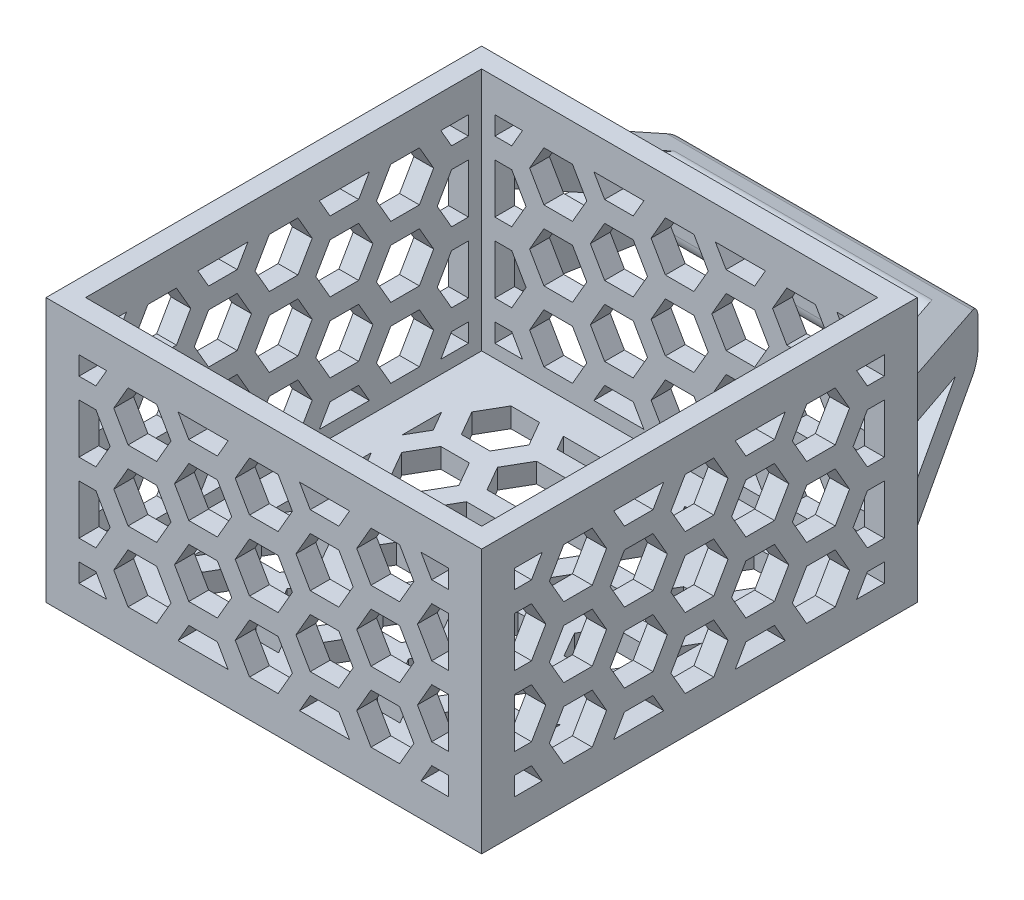
SolidWorks part; units mm, degrees
ref_plane "Front Plane" through (0, 0, 0) normal (0, 0, 1) x (1, 0, 0)
ref_plane "Top Plane" through (0, 0, 0) normal (0, 1, 0) x (1, 0, 0)
ref_plane "Right Plane" through (0, 0, 0) normal (1, 0, 0) x (0, 0, -1)
sketch "Sketch1" plane through (0, 0, 0) normal (0, 1, 0) x (1, 0, 0)
  line L0 (50, -50) -> (50, 50) construction
  line L1 (60, -60) -> (-60, -60)
  line L2 (60, -60) -> (60, 60)
  line L3 (60, 60) -> (-60, 60)
  line L4 (-60, -60) -> (-60, 60)
  line L5 (60, -60) -> (-60, 60) construction
  line L6 (60, 60) -> (-60, -60) construction
  line L7 (50, 50) -> (-50, 50) construction
  line L8 (-50, -50) -> (-50, 50) construction
  line L9 (50, -50) -> (-50, -50) construction
  line L10 (8.6603, 21.25) -> (4.3301, 28.75)
  line L11 (8.6603, 0) -> (4.3301, 7.5)
  line L12 (4.3301, 7.5) -> (-4.3301, 7.5)
  line L13 (-4.3301, 7.5) -> (-8.6603, 0)
  line L14 (-8.6603, 0) -> (-4.3301, -7.5)
  line L15 (-4.3301, -7.5) -> (4.3301, -7.5)
  line L16 (4.3301, -7.5) -> (8.6603, 0)
  line L17 (4.3301, 28.75) -> (-4.3301, 28.75)
  line L18 (-4.3301, 28.75) -> (-8.6603, 21.25)
  line L19 (-8.6603, 21.25) -> (-4.3301, 13.75)
  line L20 (-4.3301, 13.75) -> (4.3301, 13.75)
  line L21 (4.3301, 13.75) -> (8.6603, 21.25)
  line L22 (8.6603, 42.5) -> (4.3301, 50)
  line L23 (4.3301, 50) -> (-4.3301, 50)
  line L24 (-4.3301, 50) -> (-8.6603, 42.5)
  line L25 (-8.6603, 42.5) -> (-4.3301, 35)
  line L26 (-4.3301, 35) -> (4.3301, 35)
  line L27 (4.3301, 35) -> (8.6603, 42.5)
  line L28 (8.6603, -21.25) -> (4.3301, -13.75)
  line L29 (4.3301, -13.75) -> (-4.3301, -13.75)
  line L30 (-4.3301, -13.75) -> (-8.6603, -21.25)
  line L31 (-8.6603, -21.25) -> (-4.3301, -28.75)
  line L32 (-4.3301, -28.75) -> (4.3301, -28.75)
  line L33 (4.3301, -28.75) -> (8.6603, -21.25)
  line L34 (8.6603, -42.5) -> (4.3301, -35)
  line L35 (4.3301, -35) -> (-4.3301, -35)
  line L36 (-4.3301, -35) -> (-8.6603, -42.5)
  line L37 (-8.6603, -42.5) -> (-4.3301, -50)
  line L38 (-4.3301, -50) -> (4.3301, -50)
  line L39 (4.3301, -50) -> (8.6603, -42.5)
  line L40 (0, 13.75) -> (0, 7.5) construction
  line L41 (0, 10.625) -> (50, 10.625) construction
  line L42 (27.0633, 31.875) -> (22.7332, 39.375)
  line L43 (27.0633, 10.625) -> (22.7332, 18.125)
  line L44 (22.7332, 18.125) -> (14.0729, 18.125)
  line L45 (14.0729, 18.125) -> (9.7428, 10.625)
  line L46 (9.7428, 10.625) -> (14.0729, 3.125)
  line L47 (14.0729, 3.125) -> (22.7332, 3.125)
  line L48 (22.7332, 3.125) -> (27.0633, 10.625)
  line L49 (22.7332, 39.375) -> (14.0729, 39.375)
  line L50 (14.0729, 39.375) -> (9.7428, 31.875)
  line L51 (9.7428, 31.875) -> (14.0729, 24.375)
  line L52 (14.0729, 24.375) -> (22.7332, 24.375)
  line L53 (22.7332, 24.375) -> (27.0633, 31.875)
  line L57 (11.547, 50) -> (14.0729, 45.625)
  line L58 (14.0729, 45.625) -> (22.7332, 45.625)
  line L59 (22.7332, 45.625) -> (25.2591, 50)
  line L60 (22.7332, 60.625) -> (14.0729, 60.625) [skipped]
  line L61 (14.0729, 60.625) -> (13.7121, 60) [skipped]
  line L62 (23.094, 60) -> (22.7332, 60.625) [skipped]
  line L63 (11.547, 50) -> (25.2591, 50)
  line L64 (-60, 0) -> (60, 0) construction
  line L65 (0, 60) -> (0, -60) construction
  line L66 (11.547, -50) -> (14.0729, -45.625)
  line L67 (14.0729, -45.625) -> (22.7332, -45.625)
  line L68 (22.7332, -45.625) -> (25.2591, -50)
  line L69 (11.547, -50) -> (25.2591, -50)
  line L70 (22.7332, -24.375) -> (27.0633, -31.875)
  line L71 (14.0729, -24.375) -> (22.7332, -24.375)
  line L72 (9.7428, -31.875) -> (14.0729, -24.375)
  line L73 (14.0729, -39.375) -> (9.7428, -31.875)
  line L74 (22.7332, -39.375) -> (14.0729, -39.375)
  line L75 (27.0633, -31.875) -> (22.7332, -39.375)
  line L76 (22.7332, -3.125) -> (27.0633, -10.625)
  line L77 (14.0729, -3.125) -> (22.7332, -3.125)
  line L78 (9.7428, -10.625) -> (14.0729, -3.125)
  line L79 (14.0729, -18.125) -> (9.7428, -10.625)
  line L80 (22.7332, -18.125) -> (14.0729, -18.125)
  line L81 (27.0633, -10.625) -> (22.7332, -18.125)
  line L82 (45.4663, 42.5) -> (41.1362, 50)
  line L83 (41.1362, 50) -> (32.476, 50)
  line L84 (32.476, 50) -> (28.1458, 42.5)
  line L85 (28.1458, 42.5) -> (32.476, 35)
  line L86 (32.476, 35) -> (41.1362, 35)
  line L87 (41.1362, 35) -> (45.4663, 42.5)
  line L88 (45.4663, 21.25) -> (41.1362, 28.75)
  line L89 (41.1362, 28.75) -> (32.476, 28.75)
  line L90 (32.476, 28.75) -> (28.1458, 21.25)
  line L91 (28.1458, 21.25) -> (32.476, 13.75)
  line L92 (32.476, 13.75) -> (41.1362, 13.75)
  line L93 (41.1362, 13.75) -> (45.4663, 21.25)
  line L94 (45.4663, 0) -> (41.1362, 7.5)
  line L95 (41.1362, 7.5) -> (32.476, 7.5)
  line L96 (32.476, 7.5) -> (28.1458, 0)
  line L97 (28.1458, 0) -> (32.476, -7.5)
  line L98 (32.476, -7.5) -> (41.1362, -7.5)
  line L99 (41.1362, -7.5) -> (45.4663, 0)
  line L100 (45.4663, -21.25) -> (41.1362, -13.75)
  line L101 (41.1362, -13.75) -> (32.476, -13.75)
  line L102 (32.476, -13.75) -> (28.1458, -21.25)
  line L103 (28.1458, -21.25) -> (32.476, -28.75)
  line L104 (32.476, -28.75) -> (41.1362, -28.75)
  line L105 (41.1362, -28.75) -> (45.4663, -21.25)
  line L106 (45.4663, -42.5) -> (41.1362, -35)
  line L107 (41.1362, -35) -> (32.476, -35)
  line L108 (32.476, -35) -> (28.1458, -42.5)
  line L109 (28.1458, -42.5) -> (32.476, -50)
  line L110 (32.476, -50) -> (41.1362, -50)
  line L111 (41.1362, -50) -> (45.4663, -42.5)
  line L118 (50, 37.8525) -> (46.5489, 31.875)
  line L119 (46.5489, 31.875) -> (50, 25.8975)
  line L124 (50, 16.6025) -> (46.5489, 10.625)
  line L125 (46.5489, 10.625) -> (50, 4.6475)
  line L131 (50, -16.6025) -> (46.5489, -10.625)
  line L132 (46.5489, -10.625) -> (50, -4.6475)
  line L137 (50, -37.8525) -> (46.5489, -31.875)
  line L138 (46.5489, -31.875) -> (50, -25.8975)
  line L144 (50, 37.8525) -> (50, 25.8975)
  line L145 (50.879, 45.625) -> (59.5392, 45.625) [skipped]
  line L146 (59.5392, 45.625) -> (60, 46.423) [skipped]
  line L147 (50.879, 24.375) -> (59.5392, 24.375) [skipped]
  line L148 (59.5392, 39.375) -> (50.879, 39.375) [skipped]
  line L149 (63.8694, 31.875) -> (60, 38.577) [skipped]
  line L150 (60, 25.173) -> (63.8694, 31.875) [skipped]
  line L151 (59.5392, 18.125) -> (50.879, 18.125) [skipped]
  line L152 (50.879, 3.125) -> (59.5392, 3.125) [skipped]
  line L153 (63.8694, 10.625) -> (60, 17.327) [skipped]
  line L154 (59.5392, 3.125) -> (60, 3.923) [skipped]
  line L155 (59.5392, -18.125) -> (50.879, -18.125) [skipped]
  line L156 (50.879, -3.125) -> (59.5392, -3.125) [skipped]
  line L157 (60, -3.923) -> (63.8694, -10.625) [skipped]
  line L158 (60, -17.327) -> (59.5392, -18.125) [skipped]
  line L159 (59.5392, -39.375) -> (50.879, -39.375) [skipped]
  line L160 (50.879, -24.375) -> (59.5392, -24.375) [skipped]
  line L161 (60, -25.173) -> (63.8694, -31.875) [skipped]
  line L162 (63.8694, -31.875) -> (60, -38.577) [skipped]
  line L163 (50.879, -45.625) -> (59.5392, -45.625) [skipped]
  line L164 (59.5392, -45.625) -> (60, -46.423) [skipped]
  line L165 (48.3531, 50) -> (50, 47.1475) [skipped]
  line L166 (47.1304, 50) -> (50, 50) [skipped]
  line L167 (50, 16.6025) -> (50, 4.6475)
  line L168 (50, -4.6475) -> (50, -16.6025)
  line L169 (50, -25.8975) -> (50, -37.8525)
  line L170 (-46.5489, -31.875) -> (-50, -25.8975)
  line L171 (48.3531, -50) -> (48.9559, -48.9559) [skipped]
  line L172 (48.3531, -50) -> (50, -50) [skipped]
  line L173 (-50, -37.8525) -> (-46.5489, -31.875)
  line L174 (-50, -25.8975) -> (-50, -37.8525)
  line L175 (-46.5489, -10.625) -> (-50, -4.6475)
  line L176 (-50, -16.6025) -> (-46.5489, -10.625)
  line L177 (-50, -4.6475) -> (-50, -16.6025)
  line L178 (-50, 16.6025) -> (-46.5489, 10.625)
  line L179 (-46.5489, 10.625) -> (-50, 4.6475)
  line L180 (-50, 16.6025) -> (-50, 4.6475)
  line L181 (-50, 37.8525) -> (-46.5489, 31.875)
  line L182 (-46.5489, 31.875) -> (-50, 25.8975)
  line L183 (-50, 37.8525) -> (-50, 25.8975)
  line L184 (-41.1362, 35) -> (-45.4663, 42.5)
  line L185 (-32.476, 35) -> (-41.1362, 35)
  line L186 (-28.1458, 42.5) -> (-32.476, 35)
  line L187 (-32.476, 50) -> (-28.1458, 42.5)
  line L188 (-41.1362, 50) -> (-32.476, 50)
  line L189 (-45.4663, 42.5) -> (-41.1362, 50)
  line L190 (-41.1362, 13.75) -> (-45.4663, 21.25)
  line L191 (-32.476, 13.75) -> (-41.1362, 13.75)
  line L192 (-28.1458, 21.25) -> (-32.476, 13.75)
  line L193 (-32.476, 28.75) -> (-28.1458, 21.25)
  line L194 (-41.1362, 28.75) -> (-32.476, 28.75)
  line L195 (-45.4663, 21.25) -> (-41.1362, 28.75)
  line L196 (-41.1362, -7.5) -> (-45.4663, 0)
  line L197 (-32.476, -7.5) -> (-41.1362, -7.5)
  line L198 (-28.1458, 0) -> (-32.476, -7.5)
  line L199 (-32.476, 7.5) -> (-28.1458, 0)
  line L200 (-41.1362, 7.5) -> (-32.476, 7.5)
  line L201 (-45.4663, 0) -> (-41.1362, 7.5)
  line L202 (-41.1362, -28.75) -> (-45.4663, -21.25)
  line L203 (-32.476, -28.75) -> (-41.1362, -28.75)
  line L204 (-28.1458, -21.25) -> (-32.476, -28.75)
  line L205 (-32.476, -13.75) -> (-28.1458, -21.25)
  line L206 (-41.1362, -13.75) -> (-32.476, -13.75)
  line L207 (-45.4663, -21.25) -> (-41.1362, -13.75)
  line L208 (-41.1362, -50) -> (-45.4663, -42.5)
  line L209 (-32.476, -50) -> (-41.1362, -50)
  line L210 (-28.1458, -42.5) -> (-32.476, -50)
  line L211 (-32.476, -35) -> (-28.1458, -42.5)
  line L212 (-41.1362, -35) -> (-32.476, -35)
  line L213 (-45.4663, -42.5) -> (-41.1362, -35)
  line L214 (-11.547, -50) -> (-25.2591, -50)
  line L215 (-22.7332, -45.625) -> (-25.2591, -50)
  line L216 (-14.0729, -45.625) -> (-22.7332, -45.625)
  line L217 (-11.547, -50) -> (-14.0729, -45.625)
  line L218 (-14.0729, -24.375) -> (-22.7332, -24.375)
  line L219 (-9.7428, -31.875) -> (-14.0729, -24.375)
  line L220 (-14.0729, -39.375) -> (-9.7428, -31.875)
  line L221 (-22.7332, -39.375) -> (-14.0729, -39.375)
  line L222 (-27.0633, -31.875) -> (-22.7332, -39.375)
  line L223 (-22.7332, -24.375) -> (-27.0633, -31.875)
  line L224 (-14.0729, -3.125) -> (-22.7332, -3.125)
  line L225 (-9.7428, -10.625) -> (-14.0729, -3.125)
  line L226 (-14.0729, -18.125) -> (-9.7428, -10.625)
  line L227 (-22.7332, -18.125) -> (-14.0729, -18.125)
  line L228 (-27.0633, -10.625) -> (-22.7332, -18.125)
  line L229 (-22.7332, -3.125) -> (-27.0633, -10.625)
  line L230 (-22.7332, 3.125) -> (-27.0633, 10.625)
  line L231 (-14.0729, 3.125) -> (-22.7332, 3.125)
  line L232 (-9.7428, 10.625) -> (-14.0729, 3.125)
  line L233 (-14.0729, 18.125) -> (-9.7428, 10.625)
  line L234 (-22.7332, 18.125) -> (-14.0729, 18.125)
  line L235 (-27.0633, 10.625) -> (-22.7332, 18.125)
  line L236 (-11.547, 50) -> (-14.0729, 45.625)
  line L237 (-14.0729, 45.625) -> (-22.7332, 45.625)
  line L238 (-22.7332, 45.625) -> (-25.2591, 50)
  line L239 (-11.547, 50) -> (-25.2591, 50)
  line L240 (-22.7332, 24.375) -> (-27.0633, 31.875)
  line L241 (-14.0729, 24.375) -> (-22.7332, 24.375)
  line L242 (-9.7428, 31.875) -> (-14.0729, 24.375)
  line L243 (-14.0729, 39.375) -> (-9.7428, 31.875)
  line L244 (-22.7332, 39.375) -> (-14.0729, 39.375)
  line L245 (-27.0633, 31.875) -> (-22.7332, 39.375)
  circle A0 centre (0, 0) radius 7.5 construction
  circle A1 centre (18.403, 10.625) radius 7.5 construction
  point P0 (0, 0)
  dimension "D1" = 120
  dimension "D2" = 120
  dimension "D4" = 15
  dimension "D6" = 0
  dimension "D7" = 3
  dimension "D8" = 0
  dimension "D9" = 15
  dimension "D10" = 6.25
  dimension "D12" = 6.25
  dimension "D14" = 6.25
  dimension "D16" = 6.25
  dimension "D3" = 10
  dimension "D5" = 3
  dimension "D11" = 3
  dimension "D13" = 2
  dimension "D15" = 2
extrude "Boss-Extrude2" add sketch "Sketch1" along normal blind 6
sketch "Sketch2" plane through (0, 0, 60) normal (0, 0, 1) x (1, 0, 0)
  line L0 (0, 0) -> (0, 80) construction
  line L1 (-66, 40) -> (66, 40) construction
  line L2 (66, 80) -> (-66, 80)
  line L3 (66, 80) -> (66, 0)
  line L4 (66, 0) -> (-66, 0)
  line L5 (-66, 80) -> (-66, 0)
  line L6 (66, 80) -> (-66, 0) construction
  line L7 (66, 0) -> (-66, 80) construction
  line L8 (56, 70) -> (56, 10) construction
  line L9 (56, 10) -> (-56, 10) construction
  line L10 (-56, 70) -> (-56, 10) construction
  line L11 (56, 70) -> (-56, 70) construction
  line L12 (8.6603, 61.25) -> (4.3301, 68.75)
  line L13 (8.6603, 40) -> (4.3301, 47.5)
  line L14 (4.3301, 47.5) -> (-4.3301, 47.5)
  line L15 (-4.3301, 47.5) -> (-8.6603, 40)
  line L16 (-8.6603, 40) -> (-4.3301, 32.5)
  line L17 (-4.3301, 32.5) -> (4.3301, 32.5)
  line L18 (4.3301, 32.5) -> (8.6603, 40)
  line L19 (4.3301, 68.75) -> (-4.3301, 68.75)
  line L20 (-4.3301, 68.75) -> (-8.6603, 61.25)
  line L21 (-8.6603, 61.25) -> (-4.3301, 53.75)
  line L22 (-4.3301, 53.75) -> (4.3301, 53.75)
  line L23 (4.3301, 53.75) -> (8.6603, 61.25)
  line L24 (4.3301, 26.25) -> (8.6603, 18.75)
  line L25 (-4.3301, 26.25) -> (4.3301, 26.25)
  line L26 (-8.6603, 18.75) -> (-4.3301, 26.25)
  line L27 (-4.3301, 11.25) -> (-8.6603, 18.75)
  line L28 (4.3301, 11.25) -> (-4.3301, 11.25)
  line L29 (8.6603, 18.75) -> (4.3301, 11.25)
  line L30 (0, 53.75) -> (0, 47.5) construction
  line L31 (0, 50.625) -> (56, 50.625) construction
  line L32 (-60, 6) -> (-60, 0) construction
  line L33 (27.0633, 50.625) -> (22.7332, 58.125)
  line L34 (22.7332, 58.125) -> (14.0729, 58.125)
  line L35 (14.0729, 58.125) -> (9.7428, 50.625)
  line L36 (9.7428, 50.625) -> (14.0729, 43.125)
  line L37 (14.0729, 43.125) -> (22.7332, 43.125)
  line L38 (22.7332, 43.125) -> (27.0633, 50.625)
  line L39 (-60, 0) -> (60, 0) construction
  line L43 (10.8253, 70) -> (14.0729, 64.375)
  line L44 (14.0729, 64.375) -> (22.7332, 64.375)
  line L45 (22.7332, 64.375) -> (25.9808, 70)
  line L46 (14.0729, 79.375) -> (9.7428, 71.875) [skipped]
  line L47 (22.7332, 79.375) -> (14.0729, 79.375) [skipped]
  line L48 (27.0633, 71.875) -> (22.7332, 79.375) [skipped]
  line L49 (10.8253, 70) -> (25.9808, 70)
  line L50 (22.7332, 36.875) -> (27.0633, 29.375)
  line L51 (14.0729, 36.875) -> (22.7332, 36.875)
  line L52 (9.7428, 29.375) -> (14.0729, 36.875)
  line L53 (14.0729, 21.875) -> (9.7428, 29.375)
  line L54 (22.7332, 21.875) -> (14.0729, 21.875)
  line L55 (27.0633, 29.375) -> (22.7332, 21.875)
  line L56 (10.8253, 10) -> (14.0729, 15.625)
  line L57 (14.0729, 15.625) -> (22.7332, 15.625)
  line L58 (22.7332, 15.625) -> (25.9808, 10)
  line L59 (10.8253, 10) -> (25.9808, 10)
  line L60 (45.4663, 61.25) -> (41.1362, 68.75)
  line L61 (41.1362, 68.75) -> (32.476, 68.75)
  line L62 (32.476, 68.75) -> (28.1458, 61.25)
  line L63 (28.1458, 61.25) -> (32.476, 53.75)
  line L64 (32.476, 53.75) -> (41.1362, 53.75)
  line L65 (41.1362, 53.75) -> (45.4663, 61.25)
  line L66 (45.4663, 40) -> (41.1362, 47.5)
  line L67 (41.1362, 47.5) -> (32.476, 47.5)
  line L68 (32.476, 47.5) -> (28.1458, 40)
  line L69 (28.1458, 40) -> (32.476, 32.5)
  line L70 (32.476, 32.5) -> (41.1362, 32.5)
  line L71 (41.1362, 32.5) -> (45.4663, 40)
  line L72 (41.1362, 26.25) -> (45.4663, 18.75)
  line L73 (45.4663, 18.75) -> (41.1362, 11.25)
  line L74 (41.1362, 11.25) -> (32.476, 11.25)
  line L75 (32.476, 11.25) -> (28.1458, 18.75)
  line L76 (28.1458, 18.75) -> (32.476, 26.25)
  line L77 (32.476, 26.25) -> (41.1362, 26.25)
  line L78 (47.6314, 70) -> (56, 70)
  line L80 (50.879, 64.375) -> (56, 64.375)
  line L81 (47.6314, 70) -> (50.879, 64.375)
  line L83 (56, 58.125) -> (50.879, 58.125)
  line L84 (50.879, 58.125) -> (46.5489, 50.625)
  line L85 (46.5489, 50.625) -> (50.879, 43.125)
  line L86 (50.879, 43.125) -> (56, 43.125)
  line L90 (56, 21.875) -> (50.879, 21.875)
  line L91 (50.879, 21.875) -> (46.5489, 29.375)
  line L92 (46.5489, 29.375) -> (50.879, 36.875)
  line L93 (50.879, 36.875) -> (56, 36.875)
  line L94 (47.6314, 10) -> (50.879, 15.625)
  line L95 (50.879, 15.625) -> (56, 15.625)
  line L97 (47.6314, 10) -> (56, 10)
  line L98 (59.5392, 64.375) -> (62.7868, 70) [skipped]
  line L99 (63.8694, 50.625) -> (59.5392, 58.125) [skipped]
  line L100 (59.5392, 43.125) -> (63.8694, 50.625) [skipped]
  line L101 (56, 70) -> (56, 64.375)
  line L102 (56, 58.125) -> (56, 43.125)
  line L103 (56, 36.875) -> (56, 21.875)
  line L104 (59.5392, 36.875) -> (63.8694, 29.375) [skipped]
  line L105 (63.8694, 29.375) -> (59.5392, 21.875) [skipped]
  line L106 (59.5392, 15.625) -> (62.7868, 10) [skipped]
  line L107 (56, 15.625) -> (56, 10)
  line L108 (-50.879, 15.625) -> (-56, 15.625)
  line L109 (-47.6314, 10) -> (-50.879, 15.625)
  line L110 (-47.6314, 10) -> (-56, 10)
  line L111 (-56, 15.625) -> (-56, 10)
  line L112 (-50.879, 36.875) -> (-56, 36.875)
  line L113 (-46.5489, 29.375) -> (-50.879, 36.875)
  line L114 (-50.879, 21.875) -> (-46.5489, 29.375)
  line L115 (-56, 21.875) -> (-50.879, 21.875)
  line L116 (-56, 36.875) -> (-56, 21.875)
  line L117 (-56, 58.125) -> (-50.879, 58.125)
  line L118 (-50.879, 58.125) -> (-46.5489, 50.625)
  line L119 (-46.5489, 50.625) -> (-50.879, 43.125)
  line L120 (-50.879, 43.125) -> (-56, 43.125)
  line L121 (-56, 58.125) -> (-56, 43.125)
  line L122 (-47.6314, 70) -> (-56, 70)
  line L123 (-47.6314, 70) -> (-50.879, 64.375)
  line L124 (-50.879, 64.375) -> (-56, 64.375)
  line L125 (-56, 70) -> (-56, 64.375)
  line L126 (-41.1362, 53.75) -> (-45.4663, 61.25)
  line L127 (-32.476, 53.75) -> (-41.1362, 53.75)
  line L128 (-28.1458, 61.25) -> (-32.476, 53.75)
  line L129 (-32.476, 68.75) -> (-28.1458, 61.25)
  line L130 (-41.1362, 68.75) -> (-32.476, 68.75)
  line L131 (-45.4663, 61.25) -> (-41.1362, 68.75)
  line L132 (-41.1362, 32.5) -> (-45.4663, 40)
  line L133 (-32.476, 32.5) -> (-41.1362, 32.5)
  line L134 (-28.1458, 40) -> (-32.476, 32.5)
  line L135 (-32.476, 47.5) -> (-28.1458, 40)
  line L136 (-41.1362, 47.5) -> (-32.476, 47.5)
  line L137 (-45.4663, 40) -> (-41.1362, 47.5)
  line L138 (-32.476, 26.25) -> (-41.1362, 26.25)
  line L139 (-28.1458, 18.75) -> (-32.476, 26.25)
  line L140 (-32.476, 11.25) -> (-28.1458, 18.75)
  line L141 (-41.1362, 11.25) -> (-32.476, 11.25)
  line L142 (-45.4663, 18.75) -> (-41.1362, 11.25)
  line L143 (-41.1362, 26.25) -> (-45.4663, 18.75)
  line L144 (-10.8253, 10) -> (-25.9808, 10)
  line L145 (-22.7332, 15.625) -> (-25.9808, 10)
  line L146 (-14.0729, 15.625) -> (-22.7332, 15.625)
  line L147 (-10.8253, 10) -> (-14.0729, 15.625)
  line L148 (-14.0729, 36.875) -> (-22.7332, 36.875)
  line L149 (-9.7428, 29.375) -> (-14.0729, 36.875)
  line L150 (-14.0729, 21.875) -> (-9.7428, 29.375)
  line L151 (-22.7332, 21.875) -> (-14.0729, 21.875)
  line L152 (-27.0633, 29.375) -> (-22.7332, 21.875)
  line L153 (-22.7332, 36.875) -> (-27.0633, 29.375)
  line L154 (-22.7332, 43.125) -> (-27.0633, 50.625)
  line L155 (-14.0729, 43.125) -> (-22.7332, 43.125)
  line L156 (-9.7428, 50.625) -> (-14.0729, 43.125)
  line L157 (-14.0729, 58.125) -> (-9.7428, 50.625)
  line L158 (-22.7332, 58.125) -> (-14.0729, 58.125)
  line L159 (-27.0633, 50.625) -> (-22.7332, 58.125)
  line L160 (-10.8253, 70) -> (-14.0729, 64.375)
  line L161 (-14.0729, 64.375) -> (-22.7332, 64.375)
  line L162 (-22.7332, 64.375) -> (-25.9808, 70)
  line L163 (-10.8253, 70) -> (-25.9808, 70)
  circle A0 centre (0, 40) radius 7.5 construction
  circle A1 centre (18.403, 50.625) radius 7.5 construction
  point P3 (0, 40)
  dimension "D1" = 80
  dimension "D3" = 15
  dimension "D5" = 6.25
  dimension "D6" = 15
  dimension "D7" = 6.25
  dimension "D8" = 6
  dimension "D10" = 6.25
  dimension "D12" = 6.25
  dimension "D14" = 6.25
  dimension "D2" = 10
  dimension "D4" = 2
  dimension "D9" = 2
  dimension "D11" = 2
  dimension "D13" = 2
extrude "Boss-Extrude3" add sketch "Sketch2" along normal blind 6
mirror "Mirror1" about plane through (0, 0, 0) normal (0, 0, 1) of "Boss-Extrude3"
sketch "Sketch3" plane through (-60, 0, 0) normal (-1, 0, 0) x (0, 0, 1)
  line L0 (-66, 80) -> (66, 80) construction
  line L1 (66, 80) -> (66, 0) construction
  line L2 (0, 0) -> (0, 80) construction
  line L3 (-66, 80) -> (-66, 0) construction
  line L4 (60, 0) -> (-60, 0)
  line L5 (60, 0) -> (60, 80)
  line L6 (60, 80) -> (-60, 80)
  line L7 (-60, 0) -> (-60, 80)
  line L8 (60, 0) -> (-60, 80) construction
  line L9 (60, 80) -> (-60, 0) construction
  line L10 (56, 10) -> (-56, 10) construction
  line L11 (56, 10) -> (56, 70) construction
  line L12 (56, 70) -> (-56, 70) construction
  line L13 (-56, 10) -> (-56, 70) construction
  line L14 (56, 10) -> (-56, 70) construction
  line L15 (56, 70) -> (-56, 10) construction
  line L16 (-66, 40) -> (66, 40) construction
  line L17 (8.6603, 40) -> (4.3301, 47.5)
  line L18 (4.3301, 47.5) -> (-4.3301, 47.5)
  line L19 (-4.3301, 47.5) -> (-8.6603, 40)
  line L20 (-8.6603, 40) -> (-4.3301, 32.5)
  line L21 (-4.3301, 32.5) -> (4.3301, 32.5)
  line L22 (4.3301, 32.5) -> (8.6603, 40)
  line L23 (8.6603, 61.25) -> (4.3301, 68.75)
  line L24 (4.3301, 68.75) -> (-4.3301, 68.75)
  line L25 (-4.3301, 68.75) -> (-8.6603, 61.25)
  line L26 (-8.6603, 61.25) -> (-4.3301, 53.75)
  line L27 (-4.3301, 53.75) -> (4.3301, 53.75)
  line L28 (4.3301, 53.75) -> (8.6603, 61.25)
  line L29 (4.3301, 26.25) -> (8.6603, 18.75)
  line L30 (-4.3301, 26.25) -> (4.3301, 26.25)
  line L31 (-8.6603, 18.75) -> (-4.3301, 26.25)
  line L32 (-4.3301, 11.25) -> (-8.6603, 18.75)
  line L33 (4.3301, 11.25) -> (-4.3301, 11.25)
  line L34 (8.6603, 18.75) -> (4.3301, 11.25)
  line L35 (0, 53.75) -> (0, 47.5) construction
  line L36 (0, 50.625) -> (56, 50.625) construction
  line L38 (27.0633, 50.625) -> (22.7332, 58.125)
  line L39 (22.7332, 58.125) -> (14.0729, 58.125)
  line L40 (14.0729, 58.125) -> (9.7428, 50.625)
  line L41 (9.7428, 50.625) -> (14.0729, 43.125)
  line L42 (14.0729, 43.125) -> (22.7332, 43.125)
  line L43 (22.7332, 43.125) -> (27.0633, 50.625)
  line L46 (10.8253, 70) -> (14.0729, 64.375)
  line L47 (14.0729, 64.375) -> (22.7332, 64.375)
  line L48 (22.7332, 64.375) -> (25.9808, 70)
  line L49 (14.0729, 79.375) -> (9.7428, 71.875) [skipped]
  line L50 (22.7332, 79.375) -> (14.0729, 79.375) [skipped]
  line L51 (27.0633, 71.875) -> (22.7332, 79.375) [skipped]
  line L52 (10.8253, 70) -> (25.9808, 70)
  line L53 (22.7332, 36.875) -> (27.0633, 29.375)
  line L54 (14.0729, 36.875) -> (22.7332, 36.875)
  line L55 (9.7428, 29.375) -> (14.0729, 36.875)
  line L56 (14.0729, 21.875) -> (9.7428, 29.375)
  line L57 (22.7332, 21.875) -> (14.0729, 21.875)
  line L58 (27.0633, 29.375) -> (22.7332, 21.875)
  line L59 (10.8253, 10) -> (14.0729, 15.625)
  line L60 (14.0729, 15.625) -> (22.7332, 15.625)
  line L61 (22.7332, 15.625) -> (25.9808, 10)
  line L62 (10.8253, 10) -> (25.9808, 10)
  line L63 (45.4663, 61.25) -> (41.1362, 68.75)
  line L64 (41.1362, 68.75) -> (32.476, 68.75)
  line L65 (32.476, 68.75) -> (28.1458, 61.25)
  line L66 (28.1458, 61.25) -> (32.476, 53.75)
  line L67 (32.476, 53.75) -> (41.1362, 53.75)
  line L68 (41.1362, 53.75) -> (45.4663, 61.25)
  line L69 (45.4663, 40) -> (41.1362, 47.5)
  line L70 (41.1362, 47.5) -> (32.476, 47.5)
  line L71 (32.476, 47.5) -> (28.1458, 40)
  line L72 (28.1458, 40) -> (32.476, 32.5)
  line L73 (32.476, 32.5) -> (41.1362, 32.5)
  line L74 (41.1362, 32.5) -> (45.4663, 40)
  line L75 (41.1362, 26.25) -> (45.4663, 18.75)
  line L76 (45.4663, 18.75) -> (41.1362, 11.25)
  line L77 (41.1362, 11.25) -> (32.476, 11.25)
  line L78 (32.476, 11.25) -> (28.1458, 18.75)
  line L79 (28.1458, 18.75) -> (32.476, 26.25)
  line L80 (32.476, 26.25) -> (41.1362, 26.25)
  line L81 (47.6314, 70) -> (56, 70)
  line L83 (50.879, 64.375) -> (56, 64.375)
  line L84 (47.6314, 70) -> (50.879, 64.375)
  line L86 (56, 58.125) -> (50.879, 58.125)
  line L87 (50.879, 58.125) -> (46.5489, 50.625)
  line L88 (46.5489, 50.625) -> (50.879, 43.125)
  line L89 (50.879, 43.125) -> (56, 43.125)
  line L93 (56, 21.875) -> (50.879, 21.875)
  line L94 (50.879, 21.875) -> (46.5489, 29.375)
  line L95 (46.5489, 29.375) -> (50.879, 36.875)
  line L96 (50.879, 36.875) -> (56, 36.875)
  line L97 (47.6314, 10) -> (50.879, 15.625)
  line L98 (50.879, 15.625) -> (56, 15.625)
  line L100 (47.6314, 10) -> (56, 10)
  line L101 (56, 15.625) -> (56, 10)
  line L102 (60, 65.173) -> (62.7868, 70) [skipped]
  line L103 (63.8694, 50.625) -> (60, 57.327) [skipped]
  line L104 (59.5392, 43.125) -> (60, 43.923) [skipped]
  line L105 (60, 36.077) -> (63.8694, 29.375) [skipped]
  line L106 (60, 22.673) -> (59.5392, 21.875) [skipped]
  line L107 (60, 14.827) -> (62.7868, 10) [skipped]
  line L108 (56, 36.875) -> (56, 21.875)
  line L109 (56, 58.125) -> (56, 43.125)
  line L110 (56, 70) -> (56, 64.375)
  line L111 (-50.879, 15.625) -> (-56, 15.625)
  line L112 (-47.6314, 10) -> (-50.879, 15.625)
  line L113 (-47.6314, 10) -> (-56, 10)
  line L114 (-56, 15.625) -> (-56, 10)
  line L115 (-50.879, 36.875) -> (-56, 36.875)
  line L116 (-46.5489, 29.375) -> (-50.879, 36.875)
  line L117 (-50.879, 21.875) -> (-46.5489, 29.375)
  line L118 (-56, 21.875) -> (-50.879, 21.875)
  line L119 (-56, 36.875) -> (-56, 21.875)
  line L120 (-56, 58.125) -> (-50.879, 58.125)
  line L121 (-50.879, 58.125) -> (-46.5489, 50.625)
  line L122 (-46.5489, 50.625) -> (-50.879, 43.125)
  line L123 (-50.879, 43.125) -> (-56, 43.125)
  line L124 (-56, 58.125) -> (-56, 43.125)
  line L125 (-47.6314, 70) -> (-56, 70)
  line L126 (-47.6314, 70) -> (-50.879, 64.375)
  line L127 (-50.879, 64.375) -> (-56, 64.375)
  line L128 (-56, 70) -> (-56, 64.375)
  line L129 (-41.1362, 53.75) -> (-45.4663, 61.25)
  line L130 (-32.476, 53.75) -> (-41.1362, 53.75)
  line L131 (-28.1458, 61.25) -> (-32.476, 53.75)
  line L132 (-32.476, 68.75) -> (-28.1458, 61.25)
  line L133 (-41.1362, 68.75) -> (-32.476, 68.75)
  line L134 (-45.4663, 61.25) -> (-41.1362, 68.75)
  line L135 (-41.1362, 32.5) -> (-45.4663, 40)
  line L136 (-32.476, 32.5) -> (-41.1362, 32.5)
  line L137 (-28.1458, 40) -> (-32.476, 32.5)
  line L138 (-32.476, 47.5) -> (-28.1458, 40)
  line L139 (-41.1362, 47.5) -> (-32.476, 47.5)
  line L140 (-45.4663, 40) -> (-41.1362, 47.5)
  line L141 (-32.476, 26.25) -> (-41.1362, 26.25)
  line L142 (-28.1458, 18.75) -> (-32.476, 26.25)
  line L143 (-32.476, 11.25) -> (-28.1458, 18.75)
  line L144 (-41.1362, 11.25) -> (-32.476, 11.25)
  line L145 (-45.4663, 18.75) -> (-41.1362, 11.25)
  line L146 (-41.1362, 26.25) -> (-45.4663, 18.75)
  line L147 (-10.8253, 10) -> (-25.9808, 10)
  line L148 (-22.7332, 15.625) -> (-25.9808, 10)
  line L149 (-14.0729, 15.625) -> (-22.7332, 15.625)
  line L150 (-10.8253, 10) -> (-14.0729, 15.625)
  line L151 (-14.0729, 36.875) -> (-22.7332, 36.875)
  line L152 (-9.7428, 29.375) -> (-14.0729, 36.875)
  line L153 (-14.0729, 21.875) -> (-9.7428, 29.375)
  line L154 (-22.7332, 21.875) -> (-14.0729, 21.875)
  line L155 (-27.0633, 29.375) -> (-22.7332, 21.875)
  line L156 (-22.7332, 36.875) -> (-27.0633, 29.375)
  line L157 (-22.7332, 43.125) -> (-27.0633, 50.625)
  line L158 (-14.0729, 43.125) -> (-22.7332, 43.125)
  line L159 (-9.7428, 50.625) -> (-14.0729, 43.125)
  line L160 (-14.0729, 58.125) -> (-9.7428, 50.625)
  line L161 (-22.7332, 58.125) -> (-14.0729, 58.125)
  line L162 (-27.0633, 50.625) -> (-22.7332, 58.125)
  line L163 (-10.8253, 70) -> (-14.0729, 64.375)
  line L164 (-14.0729, 64.375) -> (-22.7332, 64.375)
  line L165 (-22.7332, 64.375) -> (-25.9808, 70)
  line L166 (-10.8253, 70) -> (-25.9808, 70)
  circle A0 centre (0, 40) radius 7.5 construction
  circle A1 centre (18.403, 50.625) radius 7.5 construction
  point P8 (0, 40)
  point P14 (0, 40)
  dimension "D1" = 10
  dimension "D2" = 10
  dimension "D3" = 15
  dimension "D5" = 6.25
  dimension "D6" = 15
  dimension "D7" = 6.25
  dimension "D9" = 6.25
  dimension "D11" = 6.25
  dimension "D13" = 6.25
  dimension "D4" = 2
  dimension "D8" = 2
  dimension "D10" = 2
  dimension "D12" = 2
extrude "Boss-Extrude4" add sketch "Sketch3" along normal blind 6
mirror "Mirror2" about plane through (0, 0, 0) normal (1, 0, 0) of "Boss-Extrude4"
sketch "Sketch4" plane through (0, 0, 0) normal (0, -1, 0) x (1, 0, 0)
  line L0 (-66, -66) -> (-44.4, -106)
  line L1 (-44.4, -106) -> (44.4, -106)
  line L2 (44.4, -106) -> (66, -66)
  line L3 (-56, -66) -> (-42.5, -91)
  line L4 (-66, -66) -> (66, -66) construction
  line L5 (-42.5, -91) -> (42.5, -91)
  line L6 (42.5, -91) -> (56, -66)
  line L7 (-66, -66) -> (-56, -66)
  line L8 (56, -66) -> (66, -66)
  point P10 (-42.624, -79.3101)
  point P13 (36.0846, -100.6219)
  point P14 (-52.5453, -106)
  point P15 (44.62, -106)
  point P16 (44.69, -106)
  dimension "D1" = 10
  dimension "D2" = 10
  dimension "D3" = 25
  dimension "D4" = 15
  dimension "D5" = 85
extrude "Boss-Extrude5" add sketch "Sketch4" along normal mid plane 40 from offset 40 contours L8 L2 L1 L0 L7 L3 L5 L6 offset against normal yes
sketch "Sketch5" plane through (0, 0, 0) normal (1, 0, 0) x (0, 0, -1)
  line L0 (66, 60) -> (106, 47.5)
  line L1 (106, 20) -> (106, 60) construction
  line L2 (106, 47.5) -> (106, 60)
  line L3 (106, 60) -> (66, 60)
  line L4 (66, 20) -> (106, 32.5)
  line L5 (106, 32.5) -> (106, 20)
  line L6 (106, 20) -> (66, 20)
  line L7 (66, 47.5) -> (66, 32.5)
  line L8 (66, 20) -> (66, 60) construction
  line L9 (66, 32.5) -> (91, 40)
  line L10 (91, 40) -> (66, 47.5)
  line L11 (106, 40) -> (66, 40) construction
  point P19 (66, 40)
  dimension "D1" = 15
  dimension "D2" = 15
  dimension "D3" = 15
extrude "Cut-Extrude2" cut sketch "Sketch5" against normal through all both and the other way through all contours L6 L5 L4 | L0 L2 L3 | L9 L10 L7 region at (0, 24.1667, -92.6667)
fillet "Fillet2" radius 5 1 edges at (0, 47.5, -106) type face fillet first side face at (0, 54.9219, -82.25) second side face at (0, 40, -106)
fillet "Fillet3" radius 5 1 edges at (0, 32.5, -106) type face fillet first side face at (0, 38.162, -106) second side face at (0, 25.0781, -82.25)
fillet "Fillet4" radius 5 1 edges at (0, 52.1875, -91) type face fillet first side face at (0, 55.196, -81.3728) second side face at (0, 40, -91)
fillet "Fillet5" radius 5 1 edges at (0, 27.8125, -91) type face fillet first side face at (0, 37.733, -91) second side face at (0, 24.804, -81.3728)
